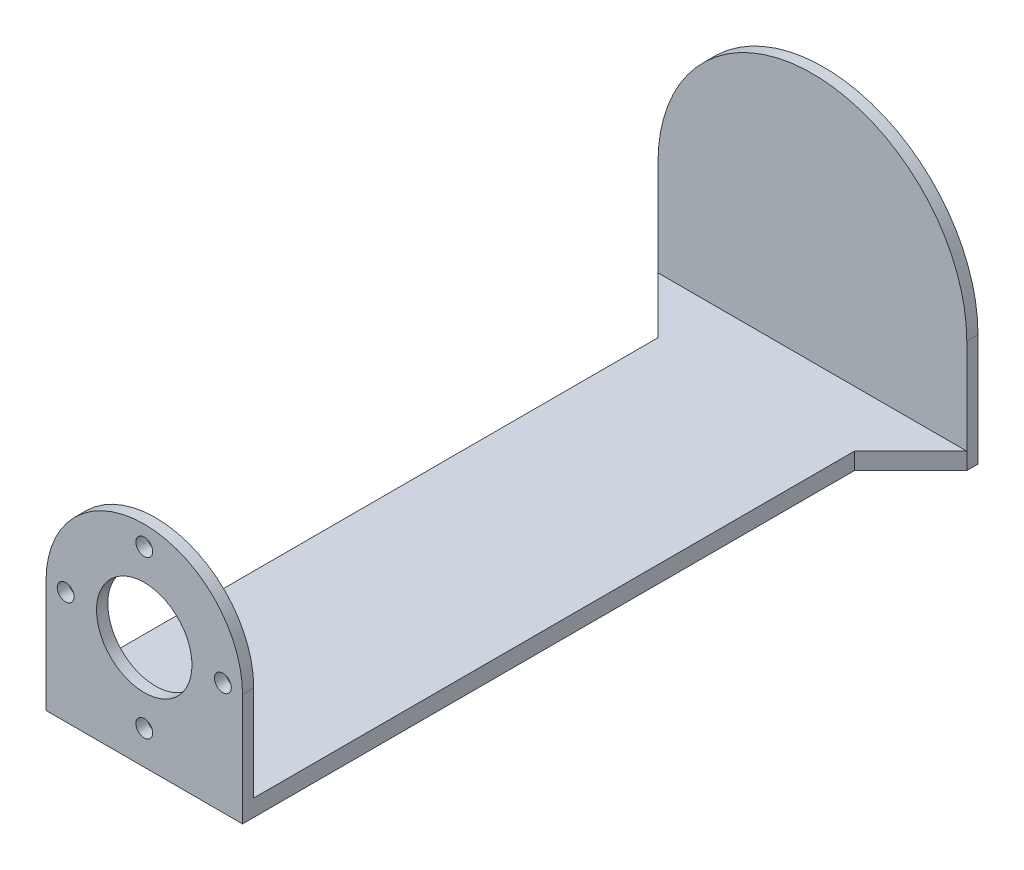
SolidWorks part; units mm, degrees
ref_plane "Front Plane" through (0, 0, 0) normal (0, 0, 1) x (1, 0, 0)
ref_plane "Top Plane" through (0, 0, 0) normal (0, 1, 0) x (1, 0, 0)
ref_plane "Right Plane" through (0, 0, 0) normal (1, 0, 0) x (0, 0, -1)
sketch "Sketch1" plane through (0, 0, 0) normal (0, 0, 1) x (1, 0, 0)
  line L0 (-17.5, 0) -> (-17.5, -20)
  line L1 (-17.5, -20) -> (17.5, -20)
  line L2 (17.5, -20) -> (17.5, 0)
  arc A0 (17.5, 0) -> (-17.5, 0) centre (0, 0) ccw
  circle A1 centre (0, 0) radius 14 construction
  circle A2 centre (0, 14) radius 1.5
  circle A4 centre (14, 0) radius 1.5
  circle A5 centre (0, -14) radius 1.5
  circle A6 centre (-14, 0) radius 1.5
  circle A7 centre (0, 0) radius 8.5
  point P18 (0, 0)
  dimension "D1" = 35
  dimension "D4" = 28
  dimension "D5" = 3
  dimension "D6" = 17
  dimension "D3" = 20
  dimension "D2" = 4
extrude "Boss-Extrude1" add sketch "Sketch1" along normal blind 2
sketch "Sketch2" plane through (0, 0, 0) normal (0, 0, -1) x (-1, 0, 0)
  line L0 (17.5, -20) -> (-17.5, -20)
  line L1 (-17.5, -20) -> (-17.5, -17)
  line L2 (-17.5, -20) -> (-17.5, 0) construction
  line L3 (-17.5, -17) -> (17.5, -17)
  line L4 (17.5, 0) -> (17.5, -20) construction
  line L5 (17.5, -17) -> (17.5, -20)
  dimension "D1" = 3
extrude "Boss-Extrude2" add sketch "Sketch2" along normal up to surface (117 mm away)
sketch "Sketch3" plane through (0, 0, -117) normal (0, 0, -1) x (-1, 0, 0)
  line L0 (-17.5, -20) -> (-27.5, -20)
  line L1 (-27.5, -20) -> (-27.5, 0)
  line L2 (17.5, -20) -> (27.5, -20)
  line L3 (27.5, -20) -> (27.5, 0)
  line L8 (17.5, -17) -> (-17.5, -17)
  line L9 (-17.5, -17) -> (-17.5, -20)
  line L10 (-17.5, -20) -> (17.5, -20)
  line L11 (17.5, -20) -> (17.5, -17)
  line L14 (-17.5, -20) -> (17.5, -20)
  arc A0 (27.5, 0) -> (-27.5, 0) centre (0, 0) ccw
  point P7 (-27.5, 0)
  point P12 (27.5, 0)
  dimension "D1" = 10
  dimension "D2" = 0
extrude "Boss-Extrude3" add sketch "Sketch3" along normal blind 2
chamfer "Chamfer1" distance 10 angle 45 2 edges at (17.5, -18.5, -117) (-17.5, -18.5, -117)
